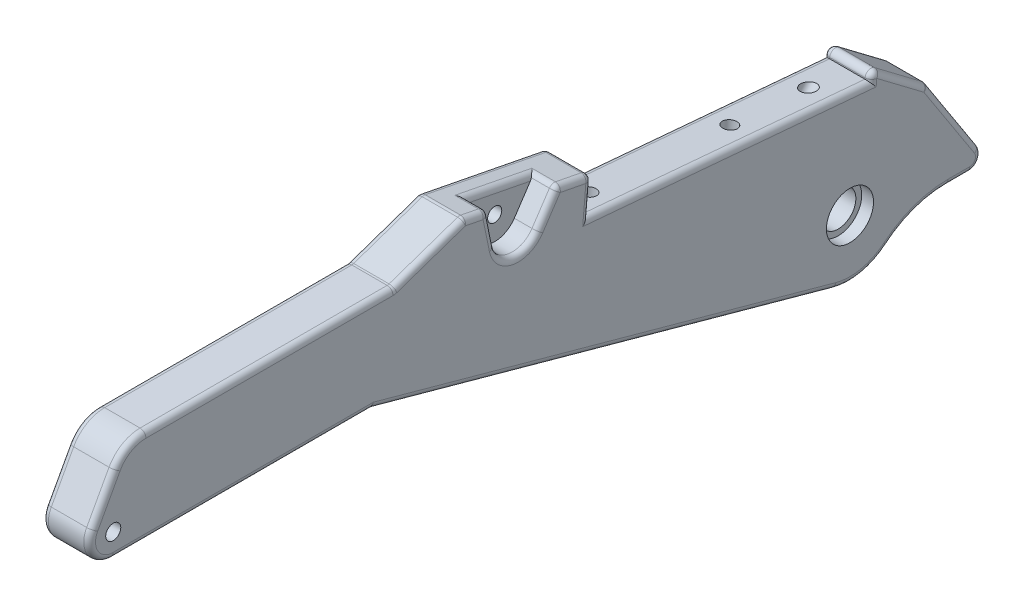
SolidWorks part; units mm, degrees
ref_plane "Front Plane" through (0, 0, 0) normal (0, 0, 1) x (1, 0, 0)
ref_plane "Top Plane" through (0, 0, 0) normal (0, 1, 0) x (1, 0, 0)
ref_plane "Right Plane" through (0, 0, 0) normal (1, 0, 0) x (0, 0, -1)
sketch "Sketch1" plane through (0, 0, 0) normal (1, 0, 0) x (0, 0, -1)
  line L0 (-5.5746, 3.0408) -> (3.158, 19.05)
  line L1 (3.158, 19.05) -> (75.6627, 19.05)
  line L3 (129.0542, 18.9233) -> (128.2241, 9.4345)
  line L4 (128.2241, 9.4345) -> (204.1341, 2.7933)
  line L6 (0, -6.35) -> (69.85, -6.35)
  line L8 (-5.5746, 3.0408) -> (7.9306, 27.7995) construction
  line L9 (129.0542, 18.9233) -> (94.7762, 25.6144)
  line L10 (94.7762, 25.6144) -> (75.6627, 19.05)
  line L12 (70.0006, 30.4506) -> (127.6524, 19.1969) construction
  line L15 (128.3624, 11.016) -> (128.9159, 17.3418) construction
  line L24 (219.6164, -5.5196) -> (233.4447, -26.8477) construction
  line L26 (219.7687, -5.7545) -> (233.4447, -26.8477)
  line L29 (69.85, 30.48) -> (129.0542, 18.9233) construction
  line L30 (206.6988, 4.2294) -> (219.393, -5.351) construction
  line L31 (204.1341, 2.7933) -> (204.161, 3.1007) construction
  line L32 (230.7807, -31.75) -> (224.8967, -31.75) construction
  line L33 (194.299, -40.7027) -> (69.85, -6.35) construction
  line L34 (206.6988, 4.2294) -> (219.393, -5.351)
  line L35 (204.1341, 2.7933) -> (204.161, 3.1007)
  line L36 (230.7807, -31.75) -> (224.8967, -31.75)
  line L37 (194.299, -40.7027) -> (69.85, -6.35)
  line L39 (-5.5746, 3.0408) -> (7.9306, 27.7995) construction
  circle A0 centre (0, 0) radius 2.032
  arc A1 (-5.5746, 3.0408) -> (0, -6.35) centre (0, 0) ccw
  arc A3 (0, -6.35) -> (-5.5746, 3.0408) centre (0, 0) ccw construction
  arc A12 (230.7807, -31.75) -> (233.4447, -26.8477) centre (230.7807, -28.575) ccw construction
  arc A13 (230.7807, -31.75) -> (233.4447, -26.8477) centre (230.7807, -28.575) ccw
  arc A14 (206.6988, 4.2294) -> (204.161, 3.1007) centre (205.7425, 2.9623) ccw construction
  arc A15 (224.8967, -31.75) -> (208.6668, -37.6115) centre (224.8967, -57.15) ccw construction
  arc A16 (194.299, -40.7027) -> (208.6668, -37.6115) centre (198.5232, -25.4) ccw construction
  arc A17 (206.6988, 4.2294) -> (204.161, 3.1007) centre (205.7425, 2.9623) ccw
  arc A18 (224.8967, -31.75) -> (208.6668, -37.6115) centre (224.8967, -57.15) ccw
  arc A19 (194.299, -40.7027) -> (208.6668, -37.6115) centre (198.5232, -25.4) ccw
  arc A20 (219.7687, -5.7545) -> (219.393, -5.351) centre (218.4366, -6.6181) ccw construction
  arc A21 (219.7687, -5.7545) -> (219.393, -5.351) centre (218.4366, -6.6181) ccw
  point P24 (87.8231, 20.9734)
  point P29 (91.946, 18.7818)
  point P32 (77.3867, 19.4539)
  point P38 (95.2451, 25.5228)
  dimension "D1" = 4.064
  dimension "D2" = 19.05
  dimension "D3" = 30
  dimension "D4" = 34.925
extrude "Boss-Extrude1" add sketch "Sketch1" along normal blind 12.7
fillet "Fillet1" radius 9.525 1 edges at (6.35, 19.05, -3.158)
sketch "Sketch2" plane through (0, 0, 0) normal (-1, 0, 0) x (0, 0, 1)
  circle A0 centre (-198.5232, -25.4) radius 4.7625
  circle A3 centre (-198.5232, -25.4) radius 6.35 construction
  dimension "D1" = 9.525
extrude "Cut-Extrude1" cut sketch "Sketch2" against normal through all
sketch "Sketch4" plane through (12.7, 0, 0) normal (1, 0, 0) x (0, 0, -1)
  circle A0 centre (198.5232, -25.4) radius 6.35
  dimension "D1" = 12.7
extrude "Cut-Extrude2" cut sketch "Sketch4" against normal blind 3.175
sketch "Sketch9" plane through (12.7, 0, 0) normal (1, 0, 0) x (0, 0, -1)
  line L0 (102.9197, 15.0665) -> (101.0086, 24.3978)
  line L2 (114.4256, 12.8206) -> (119.7057, 20.7481)
  line L3 (101.0086, 24.3978) -> (119.7057, 20.7481)
  line L4 (129.0542, 18.9233) -> (94.7762, 25.6144) construction
  arc A0 (102.9197, 15.0665) -> (114.4256, 12.8206) centre (109.1406, 16.3406) ccw
  point P1 (119.7057, 20.7481)
  point P4 (100.6977, 24.4585)
  point P11 (100.7315, 19.05)
  point P12 (101.632, 19.05)
  point P13 (128.4051, 19.05)
  dimension "D1" = 12.7
  dimension "D2" = 9.525
  dimension "D3" = 19.05
extrude "Cut-Extrude6" cut sketch "Sketch9" against normal blind 6.35
sketch "Sketch10" plane through (6.35, 0, 0) normal (1, 0, 0) x (0, 0, -1)
  circle A0 centre (109.1406, 16.3406) radius 1.905
  arc A1 (102.9197, 15.0665) -> (114.4256, 12.8206) centre (109.1406, 16.3406) ccw construction
  dimension "D1" = 3.81
extrude "Cut-Extrude7" cut sketch "Sketch10" against normal through all
fillet "Fillet2" radius 1.5875 48 edges at (0, 2.947, -204.1476) (0, 4.4128, -205.0973) (0, -0.5608, -213.0459) (0, -5.5363, -219.5985) (0, -16.3011, -226.6067) (0, -30.091, -233.5704) (0, -31.75, -227.8387) (0, -33.2603, -216.2687) (0, -40.9199, -201.8622) (0, -6.35, -34.925) (0, -3.2414, 5.4604) (0, 8.5635, 2.5621) (0, 17.7156, -3.9501) (12.7, 2.947, -204.1476) (12.7, 4.4128, -205.0973) (12.7, -0.5608, -213.0459) (12.7, -5.5363, -219.5985) (12.7, -16.3011, -226.6067) (12.7, -30.091, -233.5704) (12.7, -31.75, -227.8387) (12.7, -33.2603, -216.2687) (12.7, -40.9199, -201.8622) (12.7, -6.35, -34.925) (12.7, -3.2414, 5.4604) (12.7, 8.5635, 2.5621) (12.7, 17.7156, -3.9501) (0, -23.5263, -132.0745) (0, 6.1139, -166.1791) (0, 14.1789, -128.6392) (0, 19.05, -42.2375) (12.7, -23.5263, -132.0745) (12.7, 6.1139, -166.1791) (12.7, 14.1789, -128.6392) (12.7, 19.05, -42.2375) (12.7, 19.7322, -101.9641) (12.7, 16.7843, -117.0656) (12.7, 10.1082, -107.924) (12.7, 19.8357, -124.38) (0, 22.2688, -111.9152) (9.525, 20.7481, -119.7057) (9.525, 24.3978, -101.0086) (6.35, 22.573, -110.3571) (12.7, 25.0061, -97.8924) (12.7, 22.3322, -85.2195) (0, 22.3322, -85.2195) (6.35, 25.6144, -94.7762) (6.35, 19.05, -75.6627) (6.35, 18.9233, -129.0542)
sketch "Sketch6" plane through (0, 102.0823, -77.0424) normal (0, 0.7982, -0.6024) x (1, 0, 0)
  circle A0 centre (6.35, 152.3647) radius 1.905
  circle A1 centre (6.35, 152.3647) radius 2.286 construction
  dimension "D1" = 3.81
extrude "Cut-Extrude3" cut sketch "Sketch6" against normal blind 25.4
sketch "Sketch7" plane through (0, 20.4958, -1.7931) normal (0, 0.9962, -0.0872) x (1, 0, 0)
  circle A0 centre (6.35, 171.3639) radius 1.905
  circle A1 centre (6.35, 133.2639) radius 1.905
  circle A2 centre (6.35, 133.2639) radius 2.286 construction
  circle A3 centre (6.35, 171.3639) radius 2.286 construction
  dimension "D1" = 3.81
extrude "Cut-Extrude4" cut sketch "Sketch7" against normal blind 15.875
sketch "Sketch8" plane through (0, 98.6153, -152.0993) normal (0, 0.544, -0.8391) x (-1, 0, 0)
  circle A0 centre (-6.35, -139.9823) radius 1.905
  circle A1 centre (-6.35, -139.9823) radius 2.286 construction
  dimension "D1" = 3.81
extrude "Cut-Extrude5" cut sketch "Sketch8" against normal blind 12.7
